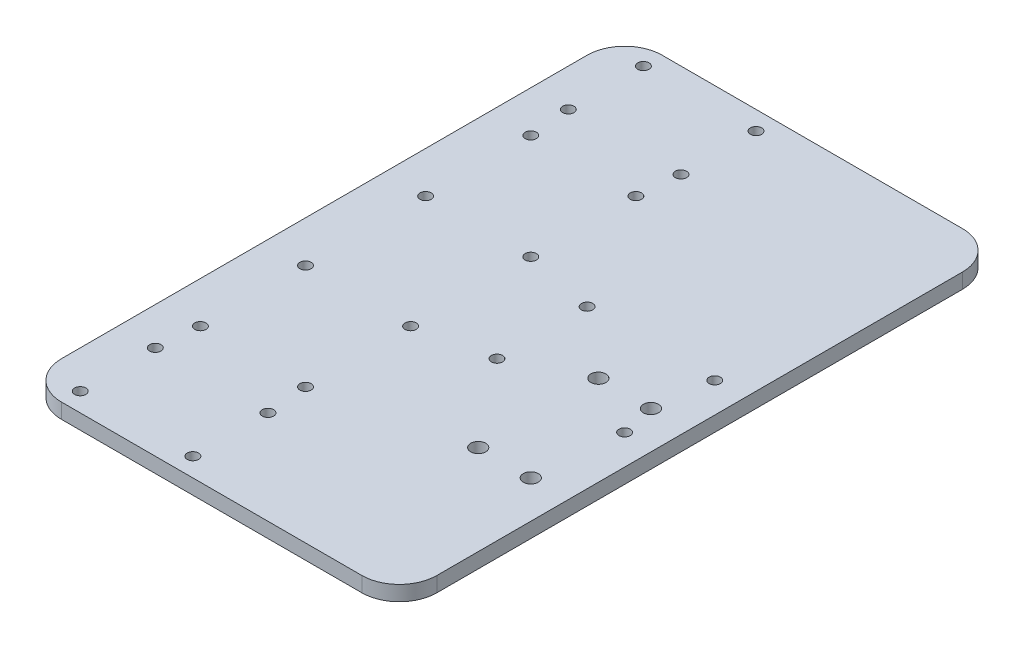
SolidWorks part; units mm, degrees
ref_plane "前视基准面" through (0, 0, 0) normal (0, 0, 1) x (1, 0, 0)
ref_plane "上视基准面" through (0, 0, 0) normal (0, 1, 0) x (1, 0, 0)
ref_plane "右视基准面" through (0, 0, 0) normal (1, 0, 0) x (0, 0, -1)
other "Configuration Table"
sketch "草图1" plane through (0, 0, 0) normal (0, 1, 0) x (1, 0, 0)
  line L0 (-50, -80) -> (50, -80)
  line L1 (-50, -80) -> (-50, 80)
  line L2 (-50, 80) -> (50, 80)
  line L3 (50, -80) -> (50, 80)
  line L4 (-50, -80) -> (50, 80) construction
  line L5 (-50, 80) -> (50, -80) construction
  point P0 (0, 0)
  dimension "D1" = 160
  dimension "D2" = 100
extrude "凸台-拉伸1" add sketch "草图1" along normal blind 4
sketch "草图2" plane through (0, 4, 0) normal (0, 1, 0) x (1, 0, 0)
  line L0 (-50, -80) -> (50, -80) construction
  line L1 (50, -80) -> (50, 80) construction
  circle A0 centre (40, -3) radius 2
  circle A1 centre (26, -3) radius 2
  circle A2 centre (40, -35) radius 2
  circle A3 centre (26, -35) radius 2
  dimension "D1" = 4
  dimension "D2" = 4
  dimension "D3" = 14
  dimension "D4" = 32
  dimension "D5" = 45
  dimension "D6" = 10
extrude "切除-拉伸1" cut sketch "草图2" against normal blind 4
sketch "草图3" plane through (0, 4, 0) normal (0, 1, 0) x (1, 0, 0)
  line L1 (-39, 44) -> (-11, 44) construction
  line L2 (-39, 44) -> (-39, 16) construction
  line L3 (-39, 16) -> (-11, 16) construction
  line L4 (-11, 44) -> (-11, 16) construction
  line L5 (-39, 44) -> (-11, 16) construction
  line L6 (-39, 16) -> (-11, 44) construction
  circle A0 centre (-39, 44) radius 1.5
  circle A1 centre (-11, 44) radius 1.5
  circle A2 centre (-11, 16) radius 1.5
  circle A3 centre (-39, 16) radius 1.5
  point P0 (-25, 30)
  dimension "D3" = 3
  dimension "D1" = 28
  dimension "D2" = 25
  dimension "D4" = 16
extrude "切除-拉伸2" cut sketch "草图3" against normal blind 4
fillet "圆角1" radius 10 4 edges at (50, 2, -80) (50, 2, 80) (-50, 2, 80) (-50, 2, -80)
mirror "镜向1" about plane through (0, 0, 0) normal (0, 0, 1) of "切除-拉伸2"
sketch "草图4" plane through (0, 4, 0) normal (0, 1, 0) x (1, 0, 0)
  line L0 (25, 80) -> (25, -80) construction
  line L1 (-50, 0) -> (50, 0) construction
  line L2 (-50, 70) -> (-50, -70) construction
  line L3 (50, -70) -> (50, 70) construction
  line L4 (40, 80) -> (-40, 80) construction
  line L5 (-40, -80) -> (40, -80) construction
  circle A0 centre (42, 12) radius 1.5
  circle A1 centre (8, 12) radius 1.5
  circle A2 centre (42, -12) radius 1.5
  circle A3 centre (8, -12) radius 1.5
  dimension "D1" = 3
  dimension "D2" = 24
  dimension "D3" = 34
  dimension "D4" = 25
extrude "切除-拉伸3" cut sketch "草图4" against normal blind 4
sketch "草图5" plane through (0, 4, 0) normal (0, 1, 0) x (1, 0, 0)
  line L0 (40, 80) -> (-40, 80) construction
  line L1 (-50, 70) -> (-50, -70) construction
  circle A0 centre (-40, 75) radius 1.5
  point P6 (-44.814, 63.4237)
  point P7 (-39.6885, 67.8373)
  dimension "D1" = 3
  dimension "D2" = 5
  dimension "D3" = 10
extrude "切除-拉伸4" cut sketch "草图5" against normal blind 10
pattern_linear "阵列(线性)1" count 2 spacing 30 along (1, 0, 0) count 2 spacing 20 along (0, 0, 1) of "切除-拉伸4"
mirror "镜向2" about plane through (0, 0, 0) normal (0, 0, 1) of "阵列(线性)1"
